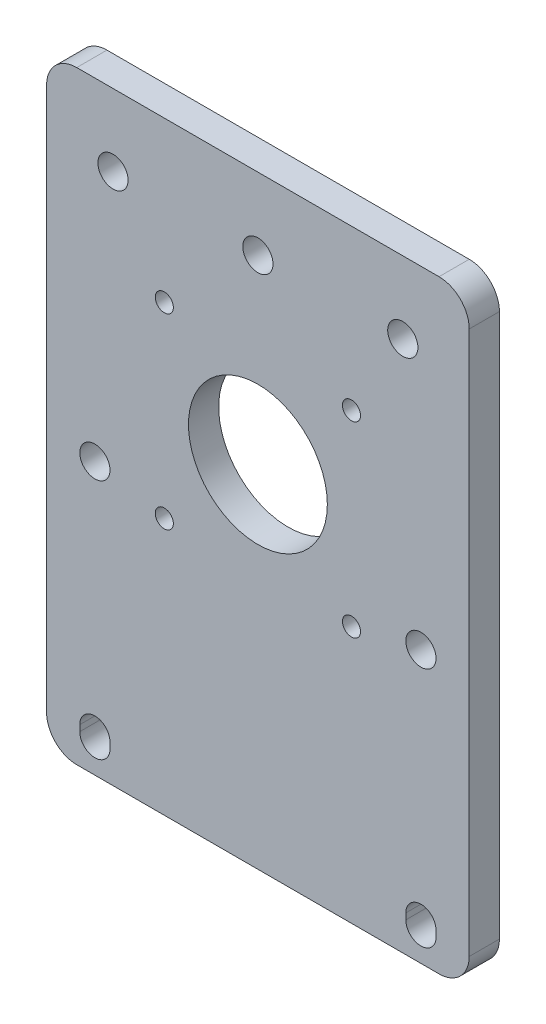
SolidWorks part; units mm, degrees
ref_plane "Front" through (0, 0, 0) normal (0, 0, 1) x (1, 0, 0)
ref_plane "Top" through (0, 0, 0) normal (0, 1, 0) x (1, 0, 0)
ref_plane "Right" through (0, 0, 0) normal (1, 0, 0) x (0, 0, -1)
sketch "Sketch4" plane through (0, 0, 0) normal (0, 0, 1) x (1, 0, 0)
  line L0 (-27, -44) -> (-27, -45) construction
  line L1 (-35, 50) -> (35, 50)
  line L2 (-35, 50) -> (-35, -50)
  line L3 (-35, -50) -> (35, -50)
  line L4 (35, 50) -> (35, -50)
  line L5 (-35, 50) -> (35, -50) construction
  line L6 (-35, -50) -> (35, 50) construction
  line L7 (-24.5, -44) -> (-24.5, -45)
  line L8 (-29.5, -44) -> (-29.5, -45)
  line L9 (0, -47.1607) -> (0, 39.6245) construction
  line L10 (27, -44) -> (27, -45) construction
  line L11 (24.5, -44) -> (24.5, -45)
  line L12 (29.5, -44) -> (29.5, -45)
  circle A0 centre (-27, -5) radius 2.5
  arc A1 (-24.5, -44) -> (-29.5, -44) centre (-27, -44) ccw
  arc A2 (-29.5, -45) -> (-24.5, -45) centre (-27, -45) ccw
  arc A3 (24.5, -44) -> (29.5, -44) centre (27, -44) cw
  arc A4 (29.5, -45) -> (24.5, -45) centre (27, -45) cw
  circle A5 centre (27, -5) radius 2.5
  point P0 (0, 0)
  point P10 (-27, -44.5)
  point P19 (27, -44.5)
  dimension "D3" = 27
  dimension "D6" = 2.5
  dimension "D8" = 5
  dimension "D1" = 70
  dimension "D2" = 100
  dimension "D4" = 39
  dimension "D5" = 1
  dimension "D7" = 5
extrude "Boss-Extrude2" add sketch "Sketch4" along normal blind 5
sketch "Sketch5" plane through (0, 0, 5) normal (0, 0, 1) x (1, 0, 0)
  line L0 (0, 46.583) -> (0, -17.262) construction
  line L1 (-44.8343, 8.0767) -> (52.8956, 8.0767) construction
  circle A0 centre (0, 8.0767) radius 11.5
  circle A1 centre (27, -5) radius 2.5 construction
  circle A2 centre (-15.5, 23.5767) radius 1.5
  circle A9 centre (15.5, 23.5767) radius 1.5
  circle A10 centre (15.5, -7.4233) radius 1.5
  circle A11 centre (-15.5, -7.4233) radius 1.5
  dimension "D1" = 23
  dimension "D3" = 3
  dimension "D2" = 30
  dimension "D4" = 15.5
  dimension "D5" = 15.5
extrude "Cut-Extrude2" cut sketch "Sketch5" against normal through all
sketch "Sketch6" plane through (0, 0, 5) normal (0, 0, 1) x (1, 0, 0)
  line L0 (0, 37.2831) -> (0, 4.0651) construction
  line L1 (-10, 48.0767) -> (10, 48.0767) construction
  line L2 (-10, 48.0767) -> (-10, 28.0767) construction
  line L3 (-10, 28.0767) -> (10, 28.0767) construction
  line L4 (10, 48.0767) -> (10, 28.0767) construction
  line L5 (-10, 48.0767) -> (10, 28.0767) construction
  line L6 (-10, 28.0767) -> (10, 48.0767) construction
  circle A0 centre (0, 8.0767) radius 11.5 construction
  circle A1 centre (24, 38.0767) radius 2.5
  circle A2 centre (-24, 38.0767) radius 2.5
  circle A3 centre (0, 38.0767) radius 2.5
  point P0 (0, 38.0767)
  dimension "D4" = 5
  dimension "D6" = 5
  dimension "D1" = 20
  dimension "D2" = 20
  dimension "D3" = 30
  dimension "D5" = 24
extrude "Cut-Extrude3" cut sketch "Sketch6" against normal through all
fillet "Fillet1" radius 5 4 edges at (-35, -50, 2.5) (35, -50, 2.5) (35, 50, 2.5) (-35, 50, 2.5)
